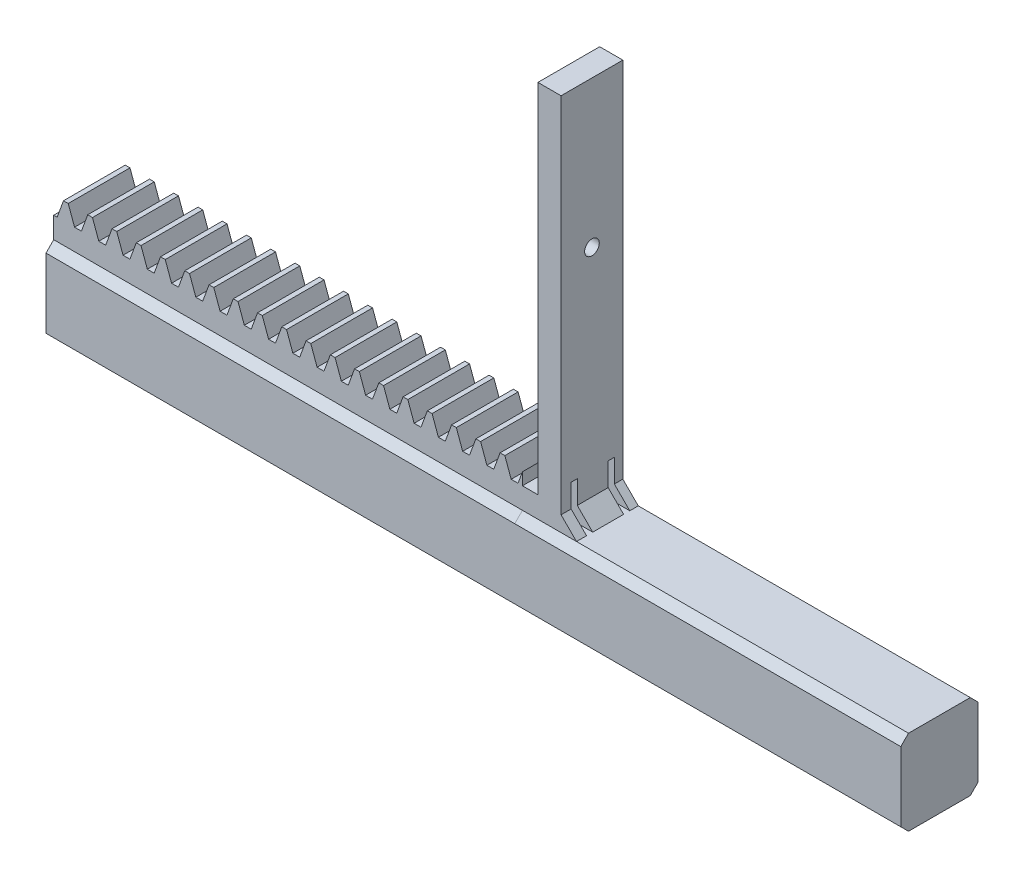
SolidWorks part; units mm, degrees
ref_plane "Front Plane" through (0, 0, 0) normal (0, 0, 1) x (1, 0, 0)
ref_plane "Top Plane" through (0, 0, 0) normal (0, 1, 0) x (1, 0, 0)
ref_plane "Right Plane" through (0, 0, 0) normal (1, 0, 0) x (0, 0, -1)
ref_plane "Plane1" through (0, 0, -3.7928) normal (0, 0, -1) x (-1, 0, 0)
sketch "Sketch1" plane through (0, 0, -3.7928) normal (0, 0, -1) x (-1, 0, 0)
  line L0 (23.517, -6.4086) -> (22.698, -8.6586)
  line L1 (22.698, -8.6586) -> (21.8092, -8.6586)
  line L2 (21.8092, -8.6586) -> (21.2359, -7.0836)
  line L3 (21.2359, -7.0836) -> (21.2359, -12.4086)
  line L4 (21.2359, -12.4086) -> (66.2359, -12.4086)
  line L5 (81.9439, -8.6586) -> (81.9439, -12.4086)
  line L6 (66.6803, -8.6586) -> (65.7915, -8.6586)
  line L7 (65.7915, -8.6586) -> (64.9725, -6.4086)
  line L8 (64.9725, -6.4086) -> (64.3577, -6.4086)
  line L9 (64.3577, -6.4086) -> (63.5387, -8.6586)
  line L10 (63.5387, -8.6586) -> (62.6499, -8.6586)
  line L11 (62.6499, -8.6586) -> (61.8309, -6.4086)
  line L12 (61.8309, -6.4086) -> (61.2161, -6.4086)
  line L13 (61.2161, -6.4086) -> (60.3971, -8.6586)
  line L14 (60.3971, -8.6586) -> (59.5083, -8.6586)
  line L15 (59.5083, -8.6586) -> (58.6893, -6.4086)
  line L16 (58.6893, -6.4086) -> (58.0745, -6.4086)
  line L17 (58.0745, -6.4086) -> (57.2555, -8.6586)
  line L18 (57.2555, -8.6586) -> (56.3667, -8.6586)
  line L19 (56.3667, -8.6586) -> (55.5477, -6.4086)
  line L20 (55.5477, -6.4086) -> (54.9329, -6.4086)
  line L21 (54.9329, -6.4086) -> (54.114, -8.6586)
  line L22 (54.114, -8.6586) -> (53.2251, -8.6586)
  line L23 (53.2251, -8.6586) -> (52.4062, -6.4086)
  line L24 (52.4062, -6.4086) -> (51.7913, -6.4086)
  line L25 (51.7913, -6.4086) -> (50.9724, -8.6586)
  line L26 (50.9724, -8.6586) -> (50.0835, -8.6586)
  line L27 (50.0835, -8.6586) -> (49.2646, -6.4086)
  line L28 (49.2646, -6.4086) -> (48.6497, -6.4086)
  line L29 (48.6497, -6.4086) -> (47.8308, -8.6586)
  line L30 (47.8308, -8.6586) -> (46.9419, -8.6586)
  line L31 (46.9419, -8.6586) -> (46.123, -6.4086)
  line L32 (46.123, -6.4086) -> (45.5081, -6.4086)
  line L33 (45.5081, -6.4086) -> (44.6892, -8.6586)
  line L34 (44.6892, -8.6586) -> (43.8003, -8.6586)
  line L35 (43.8003, -8.6586) -> (42.9814, -6.4086)
  line L36 (42.9814, -6.4086) -> (42.3665, -6.4086)
  line L37 (42.3665, -6.4086) -> (41.5476, -8.6586)
  line L38 (41.5476, -8.6586) -> (40.6587, -8.6586)
  line L39 (40.6587, -8.6586) -> (39.8398, -6.4086)
  line L40 (39.8398, -6.4086) -> (39.2249, -6.4086)
  line L41 (39.2249, -6.4086) -> (38.406, -8.6586)
  line L42 (38.406, -8.6586) -> (37.5171, -8.6586)
  line L43 (37.5171, -8.6586) -> (36.6982, -6.4086)
  line L44 (36.6982, -6.4086) -> (36.0833, -6.4086)
  line L45 (36.0833, -6.4086) -> (35.2644, -8.6586)
  line L46 (35.2644, -8.6586) -> (34.3755, -8.6586)
  line L47 (34.3755, -8.6586) -> (33.5566, -6.4086)
  line L48 (33.5566, -6.4086) -> (32.9417, -6.4086)
  line L49 (32.9417, -6.4086) -> (32.1228, -8.6586)
  line L50 (32.1228, -8.6586) -> (31.2339, -8.6586)
  line L51 (31.2339, -8.6586) -> (30.415, -6.4086)
  line L52 (30.415, -6.4086) -> (29.8001, -6.4086)
  line L53 (29.8001, -6.4086) -> (28.9812, -8.6586)
  line L54 (28.9812, -8.6586) -> (28.0923, -8.6586)
  line L55 (28.0923, -8.6586) -> (27.2734, -6.4086)
  line L56 (27.2734, -6.4086) -> (26.6586, -6.4086)
  line L57 (26.6586, -6.4086) -> (25.8396, -8.6586)
  line L58 (25.8396, -8.6586) -> (24.9508, -8.6586)
  line L59 (24.9508, -8.6586) -> (24.1318, -6.4086)
  line L60 (24.1318, -6.4086) -> (23.517, -6.4086)
  line L61 (81.4994, -8.6586) -> (81.9439, -8.6586)
  line L62 (80.6805, -6.4086) -> (81.4994, -8.6586)
  line L63 (80.0656, -6.4086) -> (80.6805, -6.4086)
  line L64 (79.2467, -8.6586) -> (80.0656, -6.4086)
  line L65 (78.3578, -8.6586) -> (79.2467, -8.6586)
  line L66 (77.5389, -6.4086) -> (78.3578, -8.6586)
  line L67 (76.924, -6.4086) -> (77.5389, -6.4086)
  line L68 (76.1051, -8.6586) -> (76.924, -6.4086)
  line L69 (75.2162, -8.6586) -> (76.1051, -8.6586)
  line L70 (74.3973, -6.4086) -> (75.2162, -8.6586)
  line L71 (73.7824, -6.4086) -> (74.3973, -6.4086)
  line L72 (72.9635, -8.6586) -> (73.7824, -6.4086)
  line L73 (72.0746, -8.6586) -> (72.9635, -8.6586)
  line L74 (71.2557, -6.4086) -> (72.0746, -8.6586)
  line L75 (70.6409, -6.4086) -> (71.2557, -6.4086)
  line L76 (69.8219, -8.6586) -> (70.6409, -6.4086)
  line L77 (68.933, -8.6586) -> (69.8219, -8.6586)
  line L78 (68.1141, -6.4086) -> (68.933, -8.6586)
  line L79 (67.4993, -6.4086) -> (68.1141, -6.4086)
  line L80 (66.6803, -8.6586) -> (67.4993, -6.4086)
  line L81 (66.2359, -12.4086) -> (81.9439, -12.4086)
extrude "Boss-Extrude1" add sketch "Sketch1" against normal blind 8
sketch "Sketch2" plane through (0, -12.4086, 0) normal (0, -1, 0) x (1, 0, 0)
  line L0 (-81.9439, 4.2072) -> (-81.9439, -3.7928) construction
  line L1 (-81.9439, 5.2072) -> (28.7641, 5.2072)
  line L2 (-81.9439, 5.2072) -> (-81.9439, -4.7928)
  line L3 (-81.9439, -4.7928) -> (28.7641, -4.7928)
  line L4 (28.7641, 5.2072) -> (28.7641, -4.7928)
  line L5 (-21.2359, 4.2072) -> (-21.2359, -3.7928) construction
  point P8 (-81.9439, 0.2072)
  dimension "D1" = 10
  dimension "D2" = 50
extrude "Boss-Extrude2" add sketch "Sketch2" along normal blind 10
chamfer "Chamfer1" distance 1 angle 45 1 edges at (-51.5899, -12.4086, 4.2072)
chamfer "Chamfer2" distance 1 angle 45 1 edges at (-51.5899, -12.4086, -3.7928)
sketch "Sketch3" plane through (0, -12.4086, 0) normal (0, 1, 0) x (1, 0, 0)
  line L1 (-21.2359, 3.7928) -> (28.7641, 3.7928)
  line L2 (-21.2359, 3.7928) -> (-21.2359, -4.2072)
  line L3 (-21.2359, -4.2072) -> (28.7641, -4.2072)
  line L4 (28.7641, 3.7928) -> (28.7641, -4.2072)
  line L6 (28.7641, 4.7928) -> (28.7641, -5.2072) construction
  dimension "D1" = 8
extrude "Boss-Extrude3" add sketch "Sketch3" along normal blind 1
chamfer "Chamfer3" distance 1 angle 45 1 edges at (3.7641, -12.4086, 4.2072)
chamfer "Chamfer4" distance 1 angle 45 1 edges at (3.7641, -12.4086, -3.7928)
sketch "Sketch4" plane through (0, -22.4086, 0) normal (0, -1, 0) x (1, 0, 0)
  line L1 (-19.2359, 4.2072) -> (-16.2359, 4.2072)
  line L2 (-19.2359, 4.2072) -> (-19.2359, -3.7928)
  line L3 (-19.2359, -3.7928) -> (-16.2359, -3.7928)
  line L4 (-16.2359, 4.2072) -> (-16.2359, -3.7928)
  line L8 (-81.9439, -4.7928) -> (28.7641, -4.7928) construction
  line L9 (28.7641, -4.7928) -> (28.7641, 5.2072) construction
  dimension "D1" = 48
  dimension "D2" = 3
  dimension "D3" = 8
  dimension "D4" = 1
extrude "Boss-Extrude6" add sketch "Sketch4" against normal blind 60
sketch "Sketch10" plane through (-16.2359, 0, 0) normal (1, 0, 0) x (0, 0, -1)
  line L0 (-4.2072, -11.4086) -> (3.7928, -11.4086) construction
  line L1 (-2.9072, -6.4086) -> (-2.1072, -6.4086)
  line L2 (-2.9072, -6.4086) -> (-2.9072, -11.4086)
  line L3 (-2.9072, -11.4086) -> (-2.1072, -11.4086)
  line L4 (-2.1072, -6.4086) -> (-2.1072, -11.4086)
  line L5 (3.7928, 37.5914) -> (3.7928, -11.4086) construction
  line L6 (1.8928, -6.4086) -> (2.6928, -6.4086)
  line L7 (1.8928, -6.4086) -> (1.8928, -11.4086)
  line L8 (1.8928, -11.4086) -> (2.6928, -11.4086)
  line L9 (2.6928, -6.4086) -> (2.6928, -11.4086)
  dimension "D1" = 0.8
  dimension "D2" = 0.8
  dimension "D3" = 4
  dimension "D4" = 1.1
  dimension "D5" = 5
  dimension "D6" = 5
extrude "Cut-Extrude4" cut sketch "Sketch10" against normal blind 4
sketch "Sketch12" plane through (-19.2359, 0, 0) normal (-1, 0, 0) x (0, 0, 1)
  line L1 (4.2072, 37.5914) -> (-3.7928, 37.5914) construction
  line L2 (4.2072, 37.5914) -> (4.2072, -11.4086) construction
  circle A0 centre (0.2072, 18.5914) radius 0.95
  dimension "D1" = 1.9
  dimension "D2" = 19
  dimension "D3" = 4
chamfer "Chamfer7" distance 2 angle 45 3 edges at (-16.2359, -11.4086, 0.1072) (-16.2359, -11.4086, -3.2428) (-16.2359, -11.4086, 3.5572)
extrude "Cut-Extrude5" cut sketch "Sketch12" against normal blind 4
chamfer "Chamfer8" distance 1 angle 45 2 edges at (-26.5899, -22.4086, 5.2072) (-26.5899, -22.4086, -4.7928)
sketch "Sketch13" plane through (0, -11.4086, 0) normal (0, 1, 0) x (1, 0, 0)
  line L1 (-21.2359, 3.7928) -> (-19.2359, 3.7928)
  line L2 (-21.2359, 3.7928) -> (-21.2359, -4.2072)
  line L3 (-21.2359, -4.2072) -> (-19.2359, -4.2072)
  line L4 (-19.2359, 3.7928) -> (-19.2359, -4.2072)
extrude "Boss-Extrude7" add sketch "Sketch13" along normal blind 2.75
